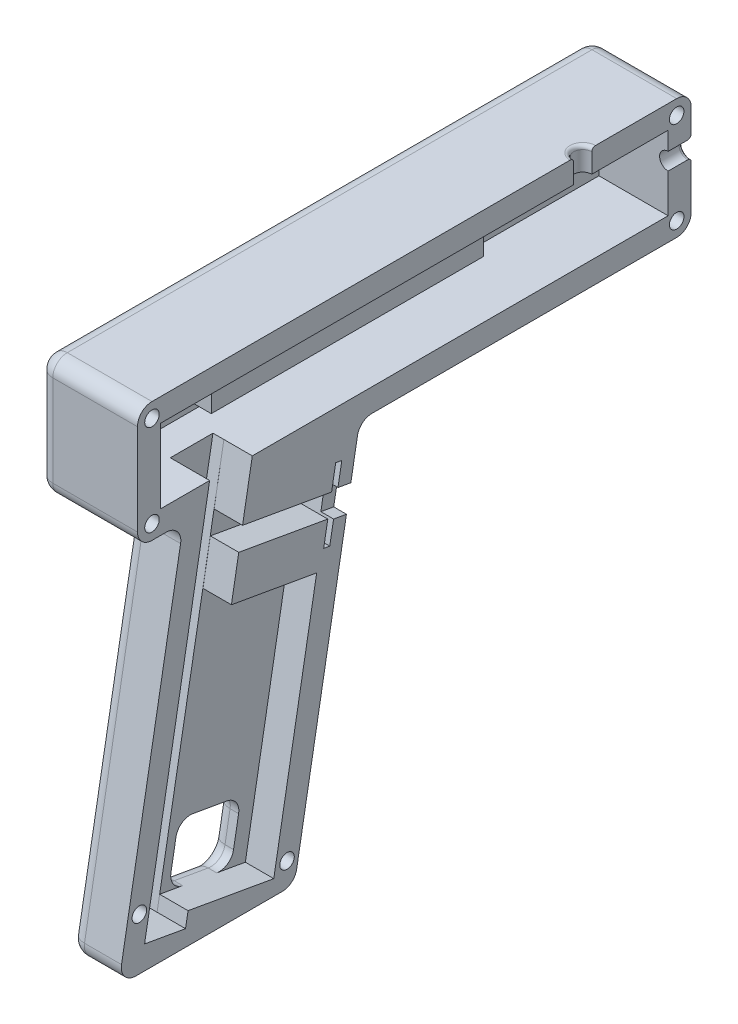
SolidWorks part; units mm, degrees
ref_plane "Front Plane" through (0, 0, 0) normal (0, 0, 1) x (1, 0, 0)
ref_plane "Top Plane" through (0, 0, 0) normal (0, 1, 0) x (1, 0, 0)
ref_plane "Right Plane" through (0, 0, 0) normal (1, 0, 0) x (0, 0, -1)
sketch "Sketch1" plane through (0, 0, 0) normal (0, 0, 1) x (1, 0, 0)
  line L1 (0, 0) -> (27.305, 0)
  line L2 (0, 0) -> (0, 33.1)
  line L3 (0, 33.1) -> (27.305, 33.1)
  line L4 (27.305, 0) -> (27.305, 33.1)
  dimension "D1" = 33.1
  dimension "D2" = 27.305
extrude "Boss-Extrude1" add sketch "Sketch1" against normal blind 152.4
sketch "Sketch2" plane through (27.305, 0, 0) normal (1, 0, 0) x (0, 0, -1)
  line L0 (0, 0) -> (0, 33.1) construction
  line L1 (6.35, 26.75) -> (146.05, 26.75)
  line L2 (6.35, 26.75) -> (6.35, 6.35)
  line L3 (6.35, 6.35) -> (146.05, 6.35)
  line L4 (146.05, 26.75) -> (146.05, 6.35)
  line L5 (152.4, 33.1) -> (0, 33.1) construction
  line L6 (152.4, 0) -> (0, 0) construction
  line L7 (152.4, 0) -> (152.4, 33.1) construction
  point P12 (6.35, 16.55)
  point P13 (0, 16.55)
  dimension "D1" = 6.35
  dimension "D2" = 6.35
  dimension "D3" = 6.35
  dimension "D4" = 6.35
extrude "Cut-Extrude1" cut sketch "Sketch2" against normal blind 19.05
sketch "Sketch4" plane through (0, 33.1, 0) normal (0, 1, 0) x (1, 0, 0)
  line L0 (27.305, 152.4) -> (27.305, 0) construction
  line L2 (27.305, 120.055) -> (27.305, 125.055)
  line L3 (27.305, 152.4) -> (0, 152.4) construction
  arc A2 (27.305, 120.055) -> (27.305, 125.055) centre (27.305, 122.555) cw
  dimension "D1" = 29.845
sketch "Sketch5" plane through (8.255, 0, 0) normal (1, 0, 0) x (0, 0, -1)
  line L0 (33.02, 17.4) -> (107.95, 17.4)
  line L1 (33.02, 23.75) -> (107.95, 23.75)
  line L2 (33.02, 23.75) -> (33.02, 9.35)
  line L3 (33.02, 9.35) -> (107.95, 9.35)
  line L4 (107.95, 23.75) -> (107.95, 9.35)
  line L9 (33.02, 15.7) -> (107.95, 15.7)
  line L10 (6.35, 6.35) -> (146.05, 6.35) construction
  line L11 (146.05, 6.35) -> (146.05, 26.75) construction
  line M13 (146.05, 6.35) -> (146.05, 26.75)
  dimension "D1" = 1.7
  dimension "D2" = 6.35
  dimension "D3" = 6.35
  dimension "D4" = 3
  dimension "D5" = 38.1
  dimension "D6" = 74.93
extrude "PCB Slot" add sketch "Sketch5" along normal blind 6.35 contours L1 L2 L0 M13 | L9 L2 L3 M13 region at (8.255, 20.575, -70.485) region at (8.255, 12.525, -70.485)
sketch "Sketch8" plane through (27.305, 0, 25.4) normal (1, 0, 0) x (0, 0, -1)
  line L0 (38.1, 0) -> (20.1852, -101.6)
  line L1 (20.1852, -101.6) -> (68.621, -101.6)
  line L2 (68.621, -101.6) -> (86.5358, 0)
  line L4 (38.1, 0) -> (86.5358, 0)
  dimension "D1" = 12.7
  dimension "D3" = 47.7
extrude "Butt" add sketch "Sketch8" against normal blind 14.175
sketch "Sketch9" plane through (27.305, 0, 25.4) normal (1, 0, 0) x (0, 0, -1)
  line L7 (68.621, -101.6) -> (86.5358, 0) construction
  line L8 (51.2564, -26.2652) -> (74.7269, -30.4036)
  line L9 (28.0575, -91.2236) -> (62.9188, -97.3706)
  line L10 (74.7269, -30.4036) -> (62.9188, -97.3706)
  line L12 (31.75, 6.35) -> (171.45, 6.35) construction
  line L13 (45.2623, 6.35) -> (57.0073, 6.35)
  line L14 (57.0073, 6.35) -> (51.2564, -26.2652)
  line L15 (45.2623, 6.35) -> (28.0575, -91.2236)
  dimension "D3" = 68
  dimension "D4" = 3.175
extrude "BatteryPack" cut sketch "Sketch9" against normal blind 7.825
sketch "Sketch10" plane through (19.48, 0, 0) normal (1, 0, 0) x (0, 0, -1)
  line L0 (33.5796, -96.676) -> (16.3455, -93.6371)
  line L2 (16.3455, -93.6371) -> (19.1238, -77.8802)
  line L3 (36.358, -80.9191) -> (19.1238, -77.8802)
  line L4 (2.6575, -91.2236) -> (37.5188, -97.3706) construction
  line L5 (36.358, -80.9191) -> (33.5796, -96.676)
  dimension "D1" = 16
extrude "BatterySwitch" cut sketch "Sketch10" against normal up to next
sketch "Sketch11" plane through (0, -88.0184, 15.52) normal (0, 0.9848, -0.1736) x (1, 0, 0)
  line L0 (19.48, 18.4579) -> (27.305, 18.4579)
  line L1 (19.48, 18.4579) -> (19.48, 29.8992)
  line L2 (27.305, 18.4579) -> (27.305, 29.8992)
  line L3 (19.48, 29.8992) -> (27.305, 29.8992)
  dimension "D1" = 11.4413
extrude "WireSpace" cut sketch "Sketch11" against normal blind 4
sketch "Sketch12" plane through (19.48, 0, 0) normal (1, 0, 0) x (0, 0, -1)
  line L0 (19.8623, 6.35) -> (31.6073, 6.35)
  line L1 (31.6073, 6.35) -> (13.2303, -97.1496)
  line L2 (13.2303, -97.1496) -> (1.9629, -95.1628)
  line L3 (1.9629, -95.1628) -> (19.8623, 6.35)
extrude "WireRoute" cut sketch "Sketch12" against normal blind 3
sketch "Sketch13" plane through (27.305, 0, 0) normal (1, 0, 0) x (0, 0, -1)
  line L0 (152.4, 33.1) -> (0, 33.1) construction
  line L1 (0, 0) -> (0, 33.1) construction
  line L3 (152.4, 0) -> (152.4, 33.1) construction
  line L7 (12.7, 0) -> (0, 0) construction
  line L8 (49.3269, -30.4036) -> (25.8564, -26.2652) construction
  line L9 (43.221, -101.6) -> (61.1358, 0) construction
  line L10 (12.7, 0) -> (-5.2148, -101.6) construction
  circle A0 centre (4, 29.1) radius 2
  circle A1 centre (148.4, 29.1) radius 2
  circle A2 centre (148.4, 4) radius 2
  circle A3 centre (4, 4) radius 2
  circle A5 centre (0.5231, -87.3425) radius 2
  circle A6 centre (41.1665, -94.9675) radius 2
  dimension "D1" = 4
  dimension "D5" = 64.5486
  dimension "D2" = 4
  dimension "D3" = 4
  dimension "D4" = 4
  dimension "D6" = 65
  dimension "D7" = 3.175
  dimension "D8" = 3.175
extrude "PressFit" cut sketch "Sketch13" against normal blind 5
extrude "HitLED" cut sketch "Sketch4" against normal up to next
sketch "Sketch15" plane through (0, 0, -146.05) normal (0, 0, 1) x (1, 0, 0)
  line L0 (27.305, 6.35) -> (27.305, 26.75) construction
  line L1 (27.305, 21.7) -> (27.305, 17)
  arc A0 (27.305, 17) -> (27.305, 21.7) centre (27.305, 19.35) cw
  dimension "D1" = 13
extrude "IRLED" cut sketch "Sketch15" against normal up to next
fillet "Fillet-LED's" radius 1 2 edges at (24.955, 19.35, -152.4) (24.805, 33.1, -122.555)
sketch "Sketch16" plane through (27.305, 0, 0) normal (1, 0, 0) x (0, 0, -1)
  line L0 (55.1893, -12.9928) -> (53.9738, -19.8865)
  line L1 (53.9738, -19.8865) -> (57.5191, -20.5116)
  line L2 (57.5191, -20.5116) -> (58.7346, -13.618)
  line L3 (58.7346, -13.618) -> (55.1893, -12.9928)
  line L4 (43.221, -101.6) -> (61.1358, 0) construction
  line L5 (49.3269, -30.4036) -> (25.8564, -26.2652) construction
  point P9 (56.962, -13.3054)
  dimension "D1" = 7
  dimension "D2" = 3.6
  dimension "D3" = 0
  dimension "D4" = 13.3054
extrude "Trigger" cut sketch "Sketch16" against normal blind 3.5
sketch "Sketch18" plane through (27.305, 0, 0) normal (1, 0, 0) x (0, 0, -1)
  line L0 (54.5614, -6.7642) -> (51.2534, -25.5248)
  line L1 (51.2534, -25.5248) -> (52.9276, -25.82)
  line L2 (52.9276, -25.82) -> (56.2356, -7.0594)
  line L3 (56.2356, -7.0594) -> (54.5614, -6.7642)
  line L4 (55.1893, -12.9928) -> (53.9738, -19.8865) construction
  line L5 (58.7346, -13.618) -> (55.1893, -12.9928) construction
  point P6 (55.3985, -6.9118)
  dimension "D1" = 0
  dimension "D2" = 1.7
  dimension "D3" = 19.05
  dimension "D4" = 6.025
extrude "ButtonPCB" cut sketch "Sketch18" against normal blind 12.065 contours L3 L0 L1 L2
sketch "Sketch20" plane through (27.305, 0, 0) normal (1, 0, 0) x (0, 0, -1)
  line L0 (28.9237, -8.8692) -> (53.4283, -13.19)
  line L1 (25.8564, -26.2652) -> (31.6073, 6.35) construction
  line L2 (54.5614, -6.7642) -> (51.2534, -25.5248) construction
  line L3 (53.4283, -13.19) -> (52.3864, -19.0989)
  line L4 (52.3864, -19.0989) -> (27.8818, -14.7781)
  line L5 (27.8818, -14.7781) -> (28.9237, -8.8692)
  line L6 (51.2534, -25.5248) -> (52.9276, -25.82) construction
  line L7 (56.2356, -7.0594) -> (54.5614, -6.7642) construction
  dimension "D1" = 6
  dimension "D2" = 6.525
extrude "ButtonWireSpace" cut sketch "Sketch20" against normal up to vertex (7.825 mm away) up to point (19.48, 6.35, -31.6073)
fillet "Fillet-Body" radius 4 24 edges at (16.305, -96.676, -33.5796) (16.305, -93.6371, -16.3455) (16.305, -77.8802, -19.1238) (16.305, -80.9191, -36.358) (20.2175, -101.6, 5.2148) (13.6525, 0, -152.4) (0, 16.55, -152.4) (13.13, -88.7975, -34.9688) (13.13, -79.3996, -27.7409) (13.13, -85.7587, -17.7347) (13.13, -95.1566, -24.9625) (13.13, -101.6, -19.0031) (20.2175, -101.6, -43.221) (13.13, -50.8, -52.1784) (20.2175, 0, -61.1358) (13.13, 0, -36.9179) (0, 0, -76.2) (13.13, -50.8, -3.7426) (20.2175, 0, -12.7) (13.6525, 0, 0) (0, 16.55, 0) (13.6525, 33.1, -152.4) (0, 33.1, -76.2) (13.6525, 33.1, 0)
